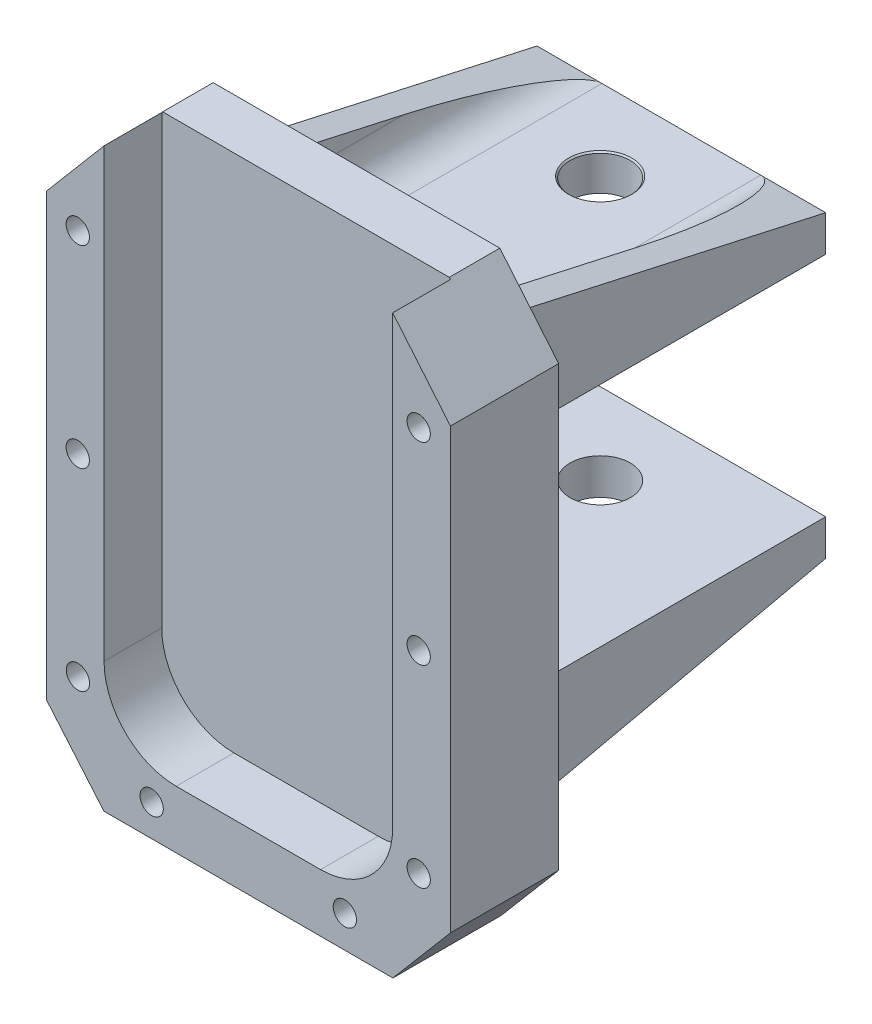
SolidWorks part; units mm, degrees
material "PLA"
ref_plane "Front Plane" through (0, 0, 0) normal (0, 0, 1) x (1, 0, 0)
ref_plane "Top Plane" through (0, 0, 0) normal (0, 1, 0) x (1, 0, 0)
ref_plane "Right Plane" through (0, 0, 0) normal (1, 0, 0) x (0, 0, -1)
sketch "Sketch1" plane through (0, 0, 0) normal (0, 0, 1) x (1, 0, 0)
  line L1 (0, 0) -> (-35.56, 0)
  line L2 (0, 0) -> (0, 50.8)
  line L3 (0, 50.8) -> (-35.56, 50.8)
  line L4 (-35.56, 0) -> (-35.56, 50.8)
  dimension "D1" = 50.8
  dimension "D2" = 35.56
extrude "Boss-Extrude1" add sketch "Sketch1" along normal blind 9.525
sketch "Sketch2" plane through (0, 0, 9.525) normal (0, 0, 1) x (1, 0, 0)
  line L0 (0, 50.8) -> (-35.56, 50.8) construction
  line L1 (-30.48, 50.8) -> (-5.08, 50.8)
  line L2 (-30.48, 50.8) -> (-30.48, 5.08)
  line L3 (-30.48, 5.08) -> (-5.08, 5.08)
  line L4 (-5.08, 50.8) -> (-5.08, 5.08)
  line L5 (-35.56, 0) -> (0, 0) construction
  line L6 (-17.78, 0) -> (-17.78, 5.08) construction
  dimension "D1" = 45.72
  dimension "D2" = 25.4
extrude "Cut-Extrude2" cut sketch "Sketch2" against normal blind 5.08
hole_wizard "Tap Drill for M2.5x0.45 Tap1" positions "Sketch6" profile "Sketch5" hole size "M2.5x0.45" standard "ANSI Metric" end condition through all
sketch "Sketch6" plane through (0, 0, 0) normal (0, 0, -1) x (-1, 0, 0)
  point P0 (2.7924, 43.0871)
  point P2 (2.7924, 26.093)
  point P4 (2.7924, 9.1052)
  point P6 (9.2907, 2.8227)
  point P8 (26.2924, 2.7871)
  point P10 (32.78, 9.1052)
  point P12 (32.7924, 26.0871)
  point P14 (32.7924, 43.0871)
sketch "Sketch5" plane through (-2.7924, 43.0871, 0) normal (1, 0, 0) x (0, 1, 0)
  line L0 (0, 0) -> (0, 9.525)
  line L1 (0, 9.525) -> (1.025, 9.525)
  line L2 (1.025, 9.525) -> (1.025, 0)
  line L5 (1.025, 0) -> (0, 0)
  line L11 (0, -6.35) -> (0, 107.95) construction
  dimension "Thru Hole Dia." = 2.05
  dimension "Thru Hole Depth" = 9.525
sketch "Sketch13" plane through (0, 0, 0) normal (0, 0, -1) x (-1, 0, 0)
  line L0 (35.56, 0) -> (0, 0) construction
  line L1 (30.48, 39.265) -> (5.08, 39.265)
  line L2 (30.48, 39.265) -> (30.48, 36.09)
  line L3 (30.48, 36.09) -> (5.08, 36.09)
  line L4 (5.08, 39.265) -> (5.08, 36.09)
  line L5 (30.48, 39.265) -> (5.08, 36.09) construction
  line L6 (30.48, 36.09) -> (5.08, 39.265) construction
  line L7 (30.48, 16.09) -> (5.08, 16.09)
  line L8 (30.48, 16.09) -> (30.48, 12.915)
  line L9 (30.48, 12.915) -> (5.08, 12.915)
  line L10 (5.08, 16.09) -> (5.08, 12.915)
  line L11 (30.48, 16.09) -> (5.08, 12.915) construction
  line L12 (30.48, 12.915) -> (5.08, 16.09) construction
  line L13 (17.78, 16.09) -> (17.78, 36.09) construction
  line L15 (0, 50.8) -> (35.56, 50.8) construction
  point P0 (17.78, 37.6775)
  point P5 (17.78, 14.5025)
  point P12 (17.78, 0)
  point P15 (17.78, 26.09)
  dimension "D1" = 3.175
  dimension "D2" = 3.175
  dimension "D3" = 25.4
  dimension "D4" = 20
  dimension "D5" = 24.71
extrude "Boss-Extrude2" add sketch "Sketch13" along normal blind 28.575
sketch "Sketch8" plane through (0, 0, 9.525) normal (0, 0, 1) x (1, 0, 0)
  line L0 (-5.179, 50.8) -> (0, 44.5915)
  line L1 (-5.08, 50.8) -> (-30.48, 50.8) construction
  line L2 (0, 0) -> (0, 50.8) construction
  line L3 (0.0027, 44.5883) -> (-5.0973, 50.5883) construction
  line L4 (0, 44.5915) -> (0, 50.8)
  line L5 (0, 50.8) -> (-5.179, 50.8)
  line L6 (-35.56, 44.7066) -> (-35.56, 50.8)
  line L7 (-35.56, 50.8) -> (-35.56, 0) construction
  line L8 (-35.56, 50.8) -> (-30.4026, 50.8)
  line L9 (-30.4026, 50.8) -> (-35.56, 44.7066)
  line L10 (-35.56, 5.97) -> (-35.56, 0)
  line L11 (-35.56, 0) -> (-30.4926, 0)
  line L12 (-35.56, 0) -> (0, 0) construction
  line L13 (-30.4926, 0) -> (-35.56, 5.97)
  line L14 (-5.0926, -0.0313) -> (0, 0)
  line L15 (0, 0) -> (0, 5.97)
  line L16 (0, 5.97) -> (-5.0926, -0.0313)
extrude "Cut-Extrude3" cut sketch "Sketch8" against normal through all
ref_plane "Plane6" through (-23.56, 0, 0) normal (-1, 0, 0) x (0, 0, 1)
fillet "Fillet1" radius 6.35 2 edges at (-5.08, 5.08, 6.985) (-30.48, 5.08, 6.985)
sketch "Sketch10" plane through (-43.87, 39.265, 0) normal (0, -1, 0) x (0, 0, -1)
  line L2 (14.2875, 13.39) -> (14.2875, 38.79) construction
  line L3 (0, 38.79) -> (0, 13.39) construction
  line L4 (14.2875, 26.09) -> (0, 26.09) construction
  line L6 (28.575, 13.39) -> (0, 13.39) construction
  line L7 (28.575, 38.79) -> (0, 38.79) construction
  line L8 (14.2875, 26.09) -> (28.575, 26.09) construction
  line L9 (28.575, 38.79) -> (28.575, 13.39) construction
  circle A0 centre (21.4312, 26.09) radius 3.175
  circle A1 centre (7.1438, 26.09) radius 3.175
  dimension "D1" = 6.35
hole_wizard "M5 Clearance Hole1" positions "3DSketch1" profile "Sketch11" hole size "M5" standard "ANSI Metric" end condition through all
sketch3d "3DSketch1"
  point P0 (-17.78, 39.265, -7.1438)
  point P3 (-17.78, 39.265, -21.4312)
sketch "Sketch11" plane through (-17.78, 39.265, -7.1438) normal (1, 0, 0) x (0, 0, 1)
  line L0 (0, 0) -> (0, 39.265)
  line L1 (0, 39.265) -> (2.65, 39.265)
  line L2 (2.65, 39.265) -> (2.65, 0.125)
  line L3 (2.65, 0.125) -> (2.775, 0)
  line L5 (2.775, 0) -> (0, 0)
  line L6 (-2.65, 0.125) -> (-2.775, 0) construction
  line L11 (0, -6.35) -> (0, 107.95) construction
  dimension "Thru Hole Dia." = 5.3
  dimension "Thru Hole Depth" = 39.265
  dimension "Near C'Sink Dia." = 5.55
  dimension "Near C'Sink Angle" = 90
sketch "Sketch14" plane through (-30.48, 0, 0) normal (-1, 0, 0) x (0, 0, 1)
  line L0 (-28.575, 12.915) -> (0, 6.565)
  line L1 (0, 44.7066) -> (0, 5.97) construction
  line L2 (-28.575, 12.915) -> (0, 12.915) construction
  dimension "D1" = 6.35
rib "Rib7" sketch "Sketch14" sketch "Sketch14" thickness 2.54 extrusion direction parallel to sketch draft on no parameters "D1"=2.54
sketch "Sketch15" plane through (-5.08, 0, 0) normal (1, 0, 0) x (0, 0, -1)
  line L0 (28.575, 12.915) -> (0, 6.565)
rib "Rib8" sketch "Sketch15" sketch "Sketch15" thickness 2.54 extrusion direction parallel to sketch draft on no parameters "D1"=2.54
sketch "Sketch16" plane through (-30.48, 0, 0) normal (-1, 0, 0) x (0, 0, 1)
  line L0 (-28.575, 39.265) -> (0, 45.615)
  line L1 (0, 44.7066) -> (0, 5.97) construction
  dimension "D1" = 6.35
sketch "Sketch17" plane through (-5.08, 0, 0) normal (1, 0, 0) x (0, 0, -1)
  line L0 (28.575, 39.265) -> (0, 45.615)
rib "Rib9" sketch "Sketch17" sketch "Sketch17" thickness 2.54 extrusion direction parallel to sketch draft on no parameters "D1"=2.54
rib "Rib10" sketch "Sketch16" sketch "Sketch16" thickness 2.54 extrusion direction parallel to sketch draft on no parameters "D1"=2.54
fillet "Fillet2" radius 3.175 2 edges at (-27.94, 12.915, -14.2875) (-7.62, 12.915, -14.2875)
fillet "Fillet3" radius 3.175 2 edges at (-7.62, 39.265, -14.2875) (-27.94, 39.265, -14.2875)
sketch "Sketch18" plane through (0, 39.265, 0) normal (0, 1, 0) x (1, 0, 0)
  line L0 (-17.78, 7.1438) -> (-17.78, 21.4312) construction
